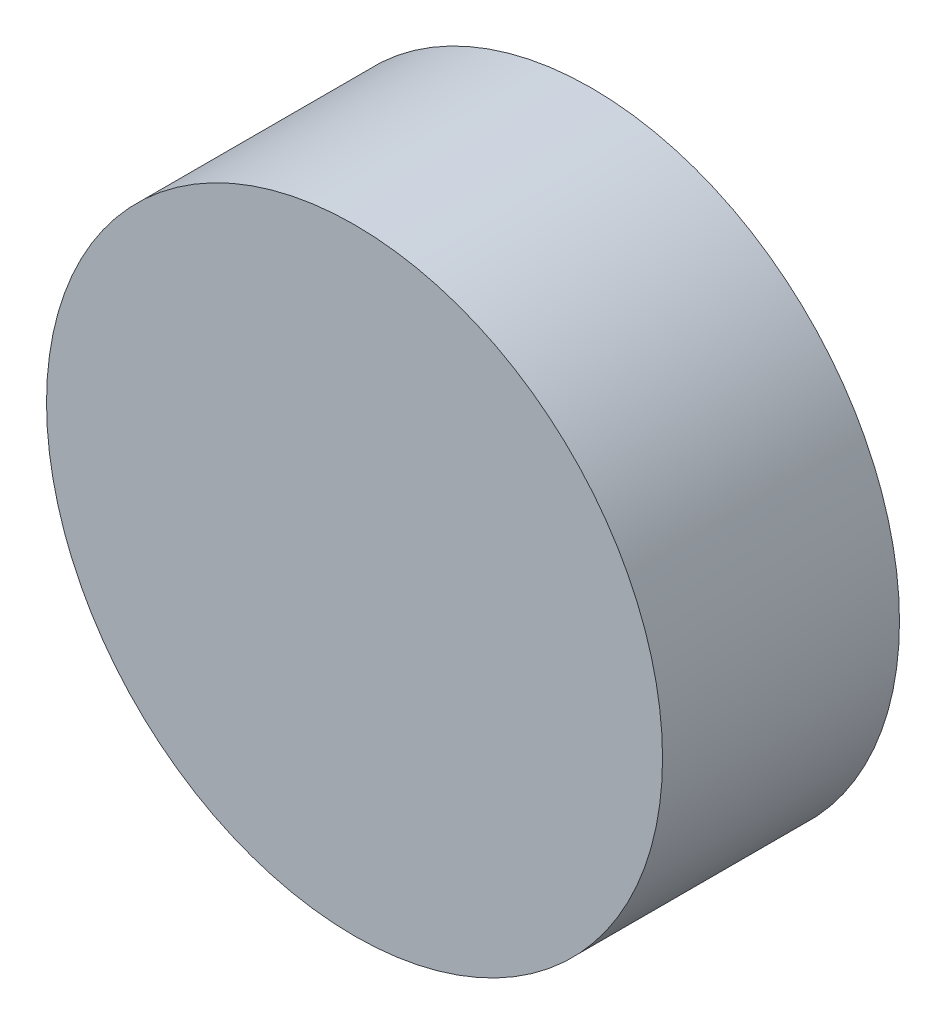
SolidWorks part; units mm, degrees
ref_plane "Спереди" through (0, 0, 0) normal (0, 0, 1) x (1, 0, 0)
ref_plane "Сверху" through (0, 0, 0) normal (0, 1, 0) x (1, 0, 0)
ref_plane "Справа" through (0, 0, 0) normal (1, 0, 0) x (0, 0, -1)
sketch "Эскиз1" plane through (0, 0, 0) normal (0, 0, 1) x (1, 0, 0)
  circle A0 centre (0, 0) radius 32.5
extrude "abot_right_wheel" add sketch "Эскиз1" along normal blind 25
ref_axis "AXIS_RIGHT_WHEEL" through (0, 0, 25) along (0, 0, -1)
